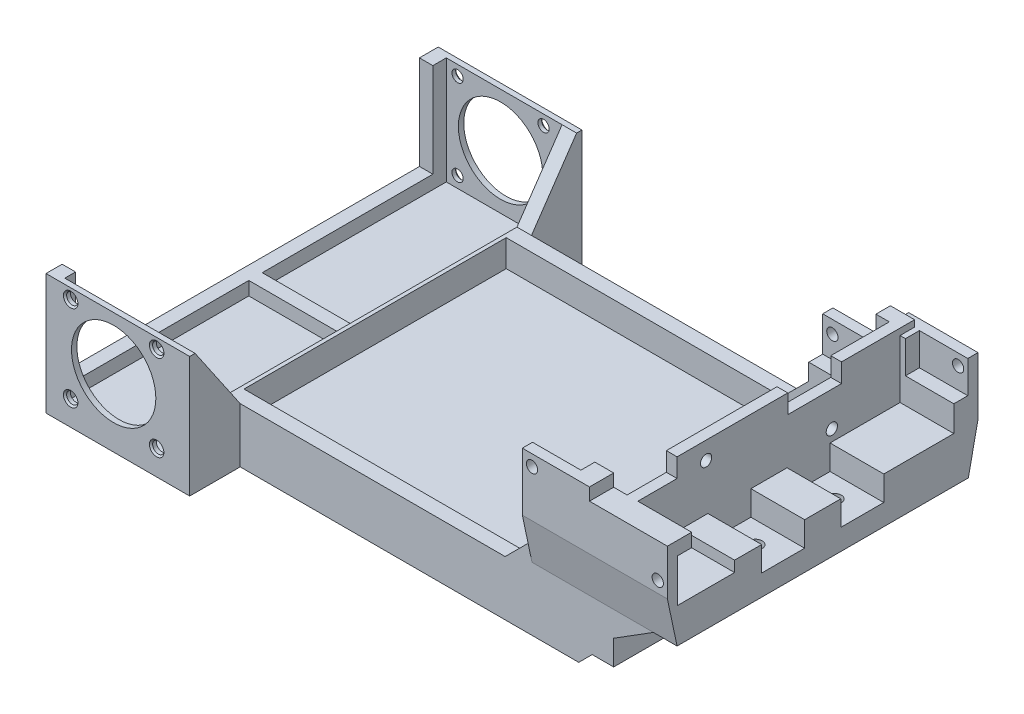
SolidWorks part; units mm, degrees
ref_plane "Front Plane" through (0, 0, 0) normal (0, 0, 1) x (1, 0, 0)
ref_plane "Top Plane" through (0, 0, 0) normal (0, 1, 0) x (1, 0, 0)
ref_plane "Right Plane" through (0, 0, 0) normal (1, 0, 0) x (0, 0, -1)
sketch "Sketch1" plane through (0, 0, 0) normal (0, 1, 0) x (1, 0, 0)
  line L0 (-12.1, 32.5) -> (-12.1, 35.5)
  line L1 (84.3983, -32.4) -> (57.3983, -32.4)
  line L2 (84.3983, -32.4) -> (84.3983, -47)
  line L3 (84.3983, -47) -> (57.3983, -47)
  line L4 (57.3983, -32.4) -> (57.3983, -47)
  line L5 (83.8, 13.5) -> (98.4, 13.5)
  line L6 (83.8, 13.5) -> (83.8, -13.5)
  line L7 (83.8, -13.5) -> (98.4, -13.5)
  line L8 (98.4, 13.5) -> (98.4, -13.5)
  line L9 (57.3983, 32.4) -> (84.3983, 32.4)
  line L10 (57.3983, 32.4) -> (57.3983, 47)
  line L11 (57.3983, 47) -> (84.3983, 47)
  line L12 (84.3983, 32.4) -> (84.3983, 47)
  line L13 (14.3, -24.25) -> (80.8, -24.25)
  line L14 (14.3, -24.25) -> (14.3, 24.25)
  line L15 (14.3, 24.25) -> (80.8, 24.25)
  line L16 (80.8, -24.25) -> (80.8, 24.25)
  line L17 (-12.1, 2.5) -> (10.1, 2.5)
  line L18 (-12.1, 2.5) -> (-12.1, 10.5)
  line L19 (-12.1, 35.5) -> (10.1, 35.5)
  line L20 (10.1, 2.5) -> (10.1, 10.5)
  line L21 (10.1, -35.5) -> (-10.1, -35.5)
  line L22 (10.1, -35.5) -> (10.1, -32.5)
  line L23 (10.1, -2.5) -> (-10.1, -2.5)
  line L24 (-10.1, -35.5) -> (-10.1, -32.5)
  line L25 (-16.1, -32.5) -> (-10.1, -32.5)
  line L26 (-16.1, -32.5) -> (-16.1, -10.5)
  line L27 (-16.1, -10.5) -> (-10.1, -10.5)
  line L28 (11.3, -32.5) -> (11.3, -10.5)
  line L29 (-16.1, 10.5) -> (-12.1, 10.5)
  line L30 (-16.1, 10.5) -> (-16.1, 32.5)
  line L31 (-16.1, 32.5) -> (-12.1, 32.5)
  line L32 (11.3, 10.5) -> (11.3, 32.5)
  line L33 (10.1, 10.5) -> (11.3, 10.5)
  line L34 (10.1, 32.5) -> (10.1, 35.5)
  line L35 (10.1, 32.5) -> (11.3, 32.5)
  line L36 (10.1, -10.5) -> (11.3, -10.5)
  line L37 (10.1, -10.5) -> (10.1, -2.5)
  line L38 (-10.1, -10.5) -> (-10.1, -2.5)
  line L39 (10.1, -32.5) -> (11.3, -32.5)
  arc A0 (86.5992, 6.7139) -> (86.5992, -6.7139) centre (90.3, 0) ccw
  arc A1 (87.5805, -8.0067) -> (93.0195, -8.0067) centre (90.3, -7.366) ccw
  arc A2 (93.0195, 8.0067) -> (87.5805, 8.0067) centre (90.3, 7.366) ccw
  arc A3 (94.0008, -6.7139) -> (94.0008, 6.7139) centre (90.3, 0) ccw
  arc A4 (93.0195, -8.0067) -> (94.0008, -6.7139) centre (94.9662, -8.4654) cw
  arc A5 (86.5992, 6.7139) -> (87.5805, 8.0067) centre (85.6338, 8.4654) ccw
  arc A6 (87.5805, -8.0067) -> (86.5992, -6.7139) centre (85.6338, -8.4654) ccw
  arc A7 (94.0008, 6.7139) -> (93.0195, 8.0067) centre (94.9662, 8.4654) cw
  point P33 (93.085, -7.1425)
  dimension "D1" = 2
  dimension "D2" = 2
  dimension "D3" = 2
  dimension "D36" = 7.6663
  dimension "D37" = 7.366
  dimension "D39" = 2.794
  dimension "D4" = 22.2
  dimension "D5" = 3
  dimension "D6" = 22
  dimension "D7" = 4
  dimension "D8" = 1.2
  dimension "D9" = 3
  dimension "D10" = 66.5
  dimension "D11" = 48.5
  dimension "D12" = 20.2
  dimension "D13" = 6
  dimension "D14" = 1.2
  dimension "D15" = 3
  dimension "D16" = 22
  dimension "D17" = 8
  dimension "D18" = 3
  dimension "D19" = 11.5
  dimension "D20" = 11.5
  dimension "D21" = 27
  dimension "D22" = 14.6
  dimension "D23" = 27
  dimension "D24" = 14.6
  dimension "D26" = 43.0983
  dimension "D27" = 8
  dimension "D28" = 5
  dimension "D29" = 8.15
  dimension "D30" = 3
  dimension "D31" = 10.75
  dimension "D32" = 9.5
  dimension "D33" = 24.25
  dimension "D34" = 27
  dimension "D35" = 14.6
  dimension "D38" = 7.366
  dimension "D40" = 14.3
  dimension "D41" = 2.5
  dimension "D42" = 43.0983
sketch "Sketch5" plane through (0, 0, 0) normal (0, 1, 0) x (1, 0, 0)
  line L0 (83.65, 27.1) -> (11.45, 27.1)
  line L1 (80.8, 24.25) -> (14.3, 24.25) construction
  line L2 (80.8, 24.25) -> (80.8, -24.25) construction
  line L3 (80.8, -24.25) -> (14.3, -24.25) construction
  line L4 (14.3, 24.25) -> (14.3, -24.25) construction
  line L5 (11.45, 27.1) -> (11.45, -27.1)
  line L6 (83.65, -27.1) -> (11.45, -27.1)
  line L7 (83.65, 27.1) -> (83.65, 3.8718)
  line L8 (83.65, -3.8718) -> (83.65, -27.1)
  line L9 (14.15, 24.4) -> (14.15, -24.4)
  line L10 (83.65, 27.1) -> (83.65, -27.1) construction
  line L11 (80.95, -24.4) -> (14.15, -24.4)
  line L12 (80.95, 24.4) -> (80.95, -24.4)
  line L13 (80.95, 24.4) -> (14.15, 24.4)
  arc A0 (83.65, 3.8718) -> (83.65, -3.8718) centre (90.3, 0) ccw
  dimension "D2" = 15.39
  dimension "D1" = 2.85
  dimension "D3" = 0.15
extrude "Boss-Extrude2" add sketch "Sketch5" along normal blind 5
sketch "Sketch6" plane through (0, 0, 0) normal (0, -1, 0) x (1, 0, 0)
  line L0 (83.65, -3.8718) -> (83.65, -27.1)
  line L1 (11.45, 27.1) -> (83.65, 27.1)
  line L2 (11.45, 27.1) -> (11.45, -27.1)
  line L3 (11.45, -27.1) -> (83.65, -27.1)
  line L4 (83.65, 27.1) -> (83.65, 3.8718)
  arc A0 (83.65, 3.8718) -> (83.65, -3.8718) centre (90.3, 0) ccw
  dimension "D1" = 15.39
extrude "Boss-Extrude4" add sketch "Sketch6" along normal blind 2.7
sketch "Sketch7" plane through (0, 5, 0) normal (0, 1, 0) x (1, 0, 0)
  line L1 (83.65, -27.1) -> (75.65, -27.1)
  line L2 (11.45, -27.1) -> (83.65, -27.1) construction
  line L3 (75.65, -27.1) -> (75.65, -24.4)
  line L4 (14.15, -24.4) -> (80.95, -24.4) construction
  line L5 (75.65, -24.4) -> (80.95, -24.4)
  line L6 (80.95, -24.4) -> (80.95, 24.4)
  line L7 (80.95, 24.4) -> (75.65, 24.4)
  line L8 (80.95, 24.4) -> (14.15, 24.4) construction
  line L9 (75.65, 24.4) -> (75.65, 27.1)
  line L10 (83.65, 27.1) -> (11.45, 27.1) construction
  line L11 (75.65, 27.1) -> (83.65, 27.1)
  line L14 (83.65, 27.1) -> (83.65, 3.8718)
  line L15 (83.65, -3.8718) -> (83.65, -27.1)
  arc A0 (83.65, 3.8718) -> (83.65, -3.8718) centre (90.3, 0) ccw
  dimension "D1" = 15.39
  dimension "D2" = 8
  dimension "D3" = 8
extrude "Boss-Extrude5" add sketch "Sketch7" along normal blind 1.575
sketch "Sketch8" plane through (0, 6.575, 0) normal (0, 1, 0) x (1, 0, 0)
  line L0 (75.65, -27.1) -> (83.65, -27.1) construction
  line L1 (80.95, -27.1) -> (98.45, -27.1)
  line L2 (80.95, -27.1) -> (80.95, 27.1)
  line L3 (80.95, 27.1) -> (98.45, 27.1)
  line L4 (98.45, -27.1) -> (98.45, 27.1)
  line L5 (80.95, -27.1) -> (83.65, -27.1) construction
  dimension "D1" = 54.2
  dimension "D2" = 17.5
  dimension "D3" = 2.7
extrude "Boss-Extrude6" add sketch "Sketch8" along normal blind 8.5
sketch "Sketch9" plane through (0, 0, 27.1) normal (0, 0, 1) x (1, 0, 0)
  line L0 (80.95, 15.075) -> (75.65, 6.575)
  line L1 (75.65, 6.575) -> (80.95, 6.575)
  line L2 (80.95, 6.575) -> (80.95, 15.075)
extrude "Boss-Extrude7" add sketch "Sketch9" against normal through all
sketch "Sketch10" plane through (0, 0, 0) normal (0, 1, 0) x (1, 0, 0)
  line L0 (80.95, 27.1) -> (80.95, -27.1) construction
  line L1 (14.15, 24.4) -> (80.95, 24.4)
  line L2 (14.15, 24.4) -> (14.15, -24.4)
  line L3 (14.15, -24.4) -> (80.95, -24.4)
  line L4 (80.95, 24.4) -> (80.95, -24.4)
  line L5 (14.15, -24.4) -> (80.95, -24.4) construction
extrude "Cut-Extrude1" cut sketch "Sketch10" along normal through all
sketch "Sketch11" plane through (0, 0, 27.1) normal (0, 0, 1) x (1, 0, 0)
  line L0 (91.05, 6.575) -> (83.65, 1.9375)
  line L1 (83.65, 6.575) -> (98.45, 6.575) construction
  line L2 (83.65, 6.575) -> (83.65, -2.7) construction
  line L3 (83.65, 1.9375) -> (83.65, 6.575)
  line L4 (83.65, 6.575) -> (91.05, 6.575)
extrude "Boss-Extrude8" add sketch "Sketch11" against normal blind 5
sketch "Sketch12" plane through (0, 0, -27.1) normal (0, 0, -1) x (-1, 0, 0)
  line L0 (-91.05, 6.575) -> (-83.65, 1.9375)
  line L1 (-98.45, 6.575) -> (-83.65, 6.575) construction
  line L2 (-83.65, 6.575) -> (-83.65, -2.7) construction
  line L3 (-83.65, 1.9375) -> (-83.65, 6.575)
  line L4 (-83.65, 6.575) -> (-91.05, 6.575)
extrude "Boss-Extrude9" add sketch "Sketch12" against normal blind 5
sketch "Sketch13" plane through (0, 15.075, 0) normal (0, 1, 0) x (1, 0, 0)
  line L1 (80.95, 27.1) -> (85.45, 27.1)
  line L2 (80.95, 27.1) -> (80.95, -27.1)
  line L3 (80.95, -27.1) -> (85.45, -27.1)
  line L4 (85.45, 27.1) -> (85.45, -27.1)
  dimension "D1" = 4.5
extrude "Boss-Extrude10" add sketch "Sketch13" along normal blind 12
sketch "Sketch15" plane through (0, 15.075, 0) normal (0, 1, 0) x (1, 0, 0)
  circle A0 centre (90.3, 7.366) radius 1.25
  circle A1 centre (90.3, -7.366) radius 1.25
  dimension "D1" = 2.5
  dimension "D2" = 2.5
extrude "Cut-Extrude3" cut sketch "Sketch15" against normal through all
sketch "Sketch16" plane through (0, 15.075, 0) normal (0, 1, 0) x (1, 0, 0)
  line L0 (90.3, -7.366) -> (90.3, 7.366) construction
  line L1 (90.3, -7.366) -> (85.45, -7.366) construction
  line L2 (85.45, -27.1) -> (85.45, 27.1) construction
  line L3 (85.45, -7.366) -> (85.45, -11.366) construction
  line L4 (90.3, 7.366) -> (85.45, 7.366) construction
  line L5 (85.45, -27.1) -> (85.45, 27.1) construction
  line L6 (85.45, 7.366) -> (85.45, 11.366) construction
  line L7 (98.45, -27.1) -> (98.45, 27.1) construction
  line L8 (85.45, 11.366) -> (98.45, 11.366)
  line L9 (85.45, 11.366) -> (85.45, 3.366)
  line L10 (85.45, -11.366) -> (98.45, -11.366)
  line L11 (98.45, 11.366) -> (98.45, 3.366)
  line L12 (85.45, -7.366) -> (85.45, -3.366) construction
  line L13 (85.45, -3.366) -> (98.45, -3.366)
  line L14 (85.45, 7.366) -> (85.45, 3.366) construction
  line L15 (85.45, 3.366) -> (98.45, 3.366)
  line L16 (85.45, -3.366) -> (85.45, -11.366)
  line L17 (98.45, -3.366) -> (98.45, -11.366)
  dimension "D1" = 4
  dimension "D2" = 4
  dimension "D3" = 4
  dimension "D4" = 4
extrude "Cut-Extrude4" cut sketch "Sketch16" against normal offset from surface (4.6 mm away) 3.9 up to face at (90.3, 6.575, -8.616)
sketch "Sketch17" plane through (0, 15.075, 0) normal (0, 1, 0) x (1, 0, 0)
  line L0 (85.45, -27.1) -> (98.45, -27.1) construction
  line L1 (98.45, 27.1) -> (95.45, 27.1)
  line L2 (98.45, 27.1) -> (98.45, -27.1)
  line L3 (98.45, -27.1) -> (95.45, -27.1)
  line L4 (95.45, 27.1) -> (95.45, -27.1)
  dimension "D1" = 3
extrude "Cut-Extrude5" cut sketch "Sketch17" against normal through all
sketch "Sketch18" plane through (80.95, 0, 0) normal (-1, 0, 0) x (0, 0, 1)
  line L0 (0, 27.075) -> (-13.5, 27.075) construction
  line L1 (-27.1, 27.075) -> (27.1, 27.075) construction
  line L3 (-13.5, 27.075) -> (-3.5, 27.075)
  line L4 (-13.5, 27.075) -> (-13.5, 23.575)
  line L5 (-13.5, 23.575) -> (-3.5, 23.575)
  line L6 (-3.5, 27.075) -> (-3.5, 23.575)
  dimension "D1" = 13.5
  dimension "D2" = 8.5
  dimension "D3" = 10
extrude "Cut-Extrude6" cut sketch "Sketch18" against normal through all
sketch "Sketch19" plane through (85.45, 0, 0) normal (1, 0, 0) x (0, 0, -1)
  line L0 (-27.1, 27.075) -> (27.1, 27.075) construction
  line L1 (0, 15.075) -> (0, 25.875) construction
  line L3 (-11.7, 20.475) -> (11.7, 20.475) construction
  line L4 (11.7, 20.475) -> (11.7, 17.175) construction
  line L5 (-11.7, 20.475) -> (-11.7, 23.775) construction
  line L7 (0, 27.075) -> (0, 25.875) construction
  line L8 (3.366, 15.075) -> (-3.366, 15.075) construction
  circle A0 centre (-11.7, 23.775) radius 1.05
  circle A1 centre (11.7, 17.175) radius 1.05
  point P11 (0, 20.475)
  point P15 (0, 20.475)
  dimension "D3" = 2.1
  dimension "D4" = 2.1
  dimension "D1" = 23.4
  dimension "D2" = 2.1
  dimension "D5" = 10.8
extrude "Cut-Extrude7" cut sketch "Sketch19" against normal through all
sketch "Sketch20" plane through (0, 27.075, 0) normal (0, 1, 0) x (1, 0, 0)
  line L2 (80.95, -24.4) -> (80.95, 24.4)
  line L4 (83.45, -24.4) -> (83.45, 24.4)
  line L5 (80.95, 27.1) -> (80.95, 24.4) construction
  line L6 (80.95, 24.4) -> (83.45, 24.4)
  line L7 (80.95, -27.1) -> (80.95, -24.4) construction
  line L8 (80.95, -24.4) -> (83.45, -24.4)
  dimension "D1" = 2
extrude "Cut-Extrude8" cut sketch "Sketch20" against normal blind 20
sketch "Sketch21" plane through (0, 0, 27.1) normal (0, 0, 1) x (1, 0, 0)
  line L0 (95.45, 15.075) -> (95.45, 17.175) construction
  line L1 (85.45, 15.075) -> (95.45, 15.075)
  line L2 (85.45, 15.075) -> (85.45, 20.075)
  line L3 (85.45, 20.075) -> (95.45, 20.075)
  line L4 (95.45, 15.075) -> (95.45, 20.075)
  line L5 (95.45, 17.175) -> (93.65, 17.175) construction
  line L6 (95.45, 6.575) -> (95.45, 15.075) construction
  circle A0 centre (93.65, 17.175) radius 1.05
  dimension "D4" = 2.1
  dimension "D1" = 5
  dimension "D2" = 2.1
  dimension "D3" = 1.8
extrude "Boss-Extrude11" add sketch "Sketch21" against normal blind 2.7 and the other way blind 1.8
sketch "Sketch23" plane through (0, 0, 27.1) normal (0, 0, 1) x (1, 0, 0)
  line L0 (68.45, 25.875) -> (68.45, 23.775) construction
  line L1 (95.45, 15.075) -> (68.45, 15.075)
  line L2 (95.45, 15.075) -> (95.45, 25.875)
  line L3 (95.45, 25.875) -> (68.45, 25.875)
  line L4 (68.45, 15.075) -> (68.45, 25.875)
  line L5 (68.45, 23.775) -> (70.25, 23.775) construction
  circle A0 centre (70.25, 23.775) radius 1.05
  circle A1 centre (93.65, 17.175) radius 1.05
  dimension "D5" = 2.1
  dimension "D6" = 2.1
  dimension "D1" = 10.8
  dimension "D2" = 27
  dimension "D3" = 2.1
  dimension "D4" = 1.8
extrude "Boss-Extrude13" add sketch "Sketch23" along normal blind 1.8 and the other way blind 2.7
sketch "Sketch22" plane through (83.45, 0, 0) normal (-1, 0, 0) x (0, 0, 1)
  line L1 (34.4916, 27.075) -> (17.1, 27.075)
  line L3 (27.9666, 23.575) -> (17.1, 23.575)
  line L4 (17.1, 27.075) -> (17.1, 23.575)
  line L5 (34.4916, 27.075) -> (34.4916, 23.575)
  line L6 (34.4916, 23.575) -> (27.9666, 23.575)
  line L7 (27.1, 27.075) -> (-3.5, 27.075) construction
  dimension "D1" = 10
  dimension "D3" = 3.5
extrude "Cut-Extrude9" cut sketch "Sketch22" against normal through all and the other way up to surface (2.5 mm away) other way up to face at (80.95, 26.475, 25.75)
sketch "Sketch24" plane through (0, 0, 27.1) normal (0, 0, 1) x (1, 0, 0)
  line L1 (68.45, 15.075) -> (85.45, 15.075)
  line L2 (68.45, 15.075) -> (68.45, 5)
  line L3 (68.45, 5) -> (85.45, 5)
  line L4 (85.45, 15.075) -> (85.45, 5)
extrude "Boss-Extrude14" add sketch "Sketch24" against normal up to surface (2.7 mm away) up to face at (68.3192, 12.2904, 24.4)
sketch "Sketch25" plane through (0, 0, -27.1) normal (0, 0, -1) x (-1, 0, 0)
  line L0 (-95.45, 25.875) -> (-95.45, 23.775) construction
  line L1 (-95.45, 15.075) -> (-68.45, 15.075)
  line L2 (-95.45, 15.075) -> (-95.45, 25.875)
  line L3 (-95.45, 25.875) -> (-82.55, 25.875)
  line L5 (-95.45, 23.775) -> (-93.65, 23.775) construction
  line L6 (-68.45, 15.075) -> (-68.45, 17.175) construction
  line L7 (-68.45, 17.175) -> (-70.25, 17.175) construction
  line L9 (-68.45, 19.575) -> (-77.45, 19.575)
  line L10 (-77.45, 19.575) -> (-82.55, 25.875)
  line L11 (-68.45, 19.575) -> (-68.45, 15.075)
  circle A0 centre (-93.65, 23.775) radius 1.05
  circle A1 centre (-70.25, 17.175) radius 1.05
  dimension "D3" = 2.1
  dimension "D1" = 2.1
  dimension "D2" = 1.8
  dimension "D4" = 2.1
  dimension "D5" = 1.8
  dimension "D6" = 4.5
  dimension "D7" = 9
  dimension "D8" = 27
  dimension "D9" = 12.9
  dimension "D10" = 6.3
extrude "Boss-Extrude15" add sketch "Sketch25" along normal blind 1.8 and the other way blind 2.7
sketch "Sketch26" plane through (0, 0, -24.4) normal (0, 0, 1) x (1, 0, 0)
  line L0 (80.95, 15.075) -> (68.45, 15.075) construction
  line L1 (68.45, 19.575) -> (80.95, 19.575)
  line L2 (68.45, 19.575) -> (68.45, 15.075)
  line L3 (68.45, 15.075) -> (80.95, 15.075)
  line L4 (80.95, 19.575) -> (80.95, 15.075)
extrude "Cut-Extrude10" cut sketch "Sketch26" against normal blind 2.6
sketch "Sketch27" plane through (0, 0, 24.4) normal (0, 0, -1) x (-1, 0, 0)
  line L1 (-68.45, 25.875) -> (-77.45, 25.875)
  line L2 (-68.45, 25.875) -> (-68.45, 19.875)
  line L3 (-68.45, 19.875) -> (-77.45, 19.875)
  line L4 (-77.45, 25.875) -> (-77.45, 19.875)
  dimension "D1" = 6
  dimension "D2" = 9
extrude "Cut-Extrude11" cut sketch "Sketch27" against normal blind 2.6
sketch "Sketch28" plane through (0, 0, -24.4) normal (0, 0, 1) x (1, 0, 0)
  line L1 (95.45, 25.875) -> (86.45, 25.875)
  line L2 (95.45, 25.875) -> (95.45, 19.875)
  line L3 (95.45, 19.875) -> (86.45, 19.875)
  line L4 (86.45, 25.875) -> (86.45, 19.875)
  dimension "D1" = 6
  dimension "D2" = 9
extrude "Cut-Extrude12" cut sketch "Sketch28" against normal blind 2.6
sketch "Sketch29" plane through (0, 0, 24.4) normal (0, 0, -1) x (-1, 0, 0)
  line L0 (-95.45, 15.075) -> (-95.45, 13.075)
  line L2 (-95.45, 15.075) -> (-95.45, 21.075)
  line L3 (-95.45, 21.075) -> (-86.45, 21.075)
  line L5 (-95.45, 13.075) -> (-86.45, 13.075)
  line L6 (-86.45, 13.075) -> (-86.45, 21.075)
  dimension "D1" = 6
  dimension "D2" = 9
  dimension "D3" = 2
extrude "Cut-Extrude13" cut sketch "Sketch29" against normal blind 2.6 and the other way blind 8
sketch "Sketch30" plane through (0, 0, -27.1) normal (0, 0, -1) x (-1, 0, 0)
  line L1 (-68.45, 15.075) -> (-86.6707, 15.075)
  line L2 (-68.45, 15.075) -> (-68.45, 5)
  line L3 (-68.45, 5) -> (-86.6707, 5)
  line L4 (-86.6707, 15.075) -> (-86.6707, 5)
extrude "Boss-Extrude16" add sketch "Sketch30" against normal blind 2.7
sketch "Sketch31" plane through (0, -2.7, 0) normal (0, -1, 0) x (1, 0, 0)
  line L0 (83.65, 27.1) -> (77.15, 27.1) construction
  line L1 (83.65, 27.1) -> (11.45, 27.1) construction
  line L3 (77.15, 27.1) -> (-12.5923, 27.1)
  line L4 (77.15, 27.1) -> (77.15, -27.7093)
  line L5 (77.15, -27.7093) -> (-12.5923, -27.7093)
  line L6 (-12.5923, 27.1) -> (-12.5923, -27.7093)
  dimension "D1" = 6.5
  dimension "D2" = 24.05
extrude "Boss-Extrude17" add sketch "Sketch31" along normal blind 2.5
sketch "Sketch33" plane through (0, -5.2, 0) normal (0, -1, 0) x (1, 0, 0)
  line L0 (-12.6, 0) -> (0, 0) construction
  line L1 (-12.5923, 27.1) -> (-12.5923, -27.7093) construction
  line L2 (-12.6, -1.25) -> (11.45, -1.25)
  line L3 (-12.6, 1.25) -> (11.45, 1.25)
  line L4 (0, 0) -> (11.45, 0) construction
  line L5 (11.45, 27.1) -> (11.45, -27.1) construction
  line L6 (-12.6, -1.25) -> (0, -1.25) construction
  line L7 (-12.6, 1.25) -> (0, 1.25) construction
  line L8 (-12.6, 1.25) -> (-12.6, -1.25)
  line L9 (11.45, 1.25) -> (11.45, -1.25)
  dimension "D1" = 1.25
  dimension "D2" = 1.25
extrude "Boss-Extrude18" add sketch "Sketch33" against normal blind 5
sketch "Sketch36" plane through (0, -5.2, 0) normal (0, -1, 0) x (1, 0, 0)
  line L1 (-12.5923, 27.1) -> (11.45, 27.1)
  line L2 (-12.5923, 27.1) -> (-12.5923, 36.5)
  line L3 (-12.5923, 36.5) -> (11.45, 36.5)
  line L4 (11.45, 27.1) -> (11.45, 36.5)
  dimension "D1" = 9.4
extrude "Boss-Extrude20" add sketch "Sketch36" against normal up to surface (2.5 mm away) up to face at (-0.5711, -2.7, 14.175)
sketch "Sketch37" plane through (0, -2.7, 0) normal (0, 1, 0) x (1, 0, 0)
  line L0 (11.45, -27.1) -> (11.45, -36.5) construction
  line L1 (-12.5923, -36.5) -> (11.45, -36.5)
  line L2 (-12.5923, -36.5) -> (-12.5923, -35.5)
  line L3 (-12.5923, -35.5) -> (11.45, -35.5)
  line L4 (11.45, -36.5) -> (11.45, -35.5)
  dimension "D1" = 1
extrude "Boss-Extrude21" add sketch "Sketch37" along normal blind 20
sketch "Sketch38" plane through (0, 0, 36.5) normal (0, 0, 1) x (1, 0, 0)
  line L0 (0, 17.3) -> (8, 17.3) construction
  line L1 (-12.5923, 17.3) -> (11.45, 17.3) construction
  line L2 (8, 17.3) -> (8, 15.4) construction
  line L3 (8, 15.4) -> (-8, 15.4) construction
  line L4 (8, 15.4) -> (8, -0.6) construction
  line L5 (-8, 15.4) -> (-8, -0.6) construction
  line L6 (-8, -0.6) -> (-8, 7.4) construction
  line L7 (-8, 7.4) -> (0, 7.4) construction
  circle A0 centre (8, 15.4) radius 1.05
  circle A1 centre (8, -0.6) radius 1.05
  circle A2 centre (-8, 15.4) radius 1.05
  circle A3 centre (-8, -0.6) radius 1.05
  circle A4 centre (0, 7.4) radius 7.85
  dimension "D3" = 2.1
  dimension "D8" = 15.7
  dimension "D1" = 8
  dimension "D2" = 1.9
  dimension "D4" = 16
  dimension "D5" = 16
  dimension "D6" = 16
  dimension "D7" = 8
extrude "Cut-Extrude14" cut sketch "Sketch38" against normal up to next
sketch "Sketch39" plane through (0, -2.7, 0) normal (0, 1, 0) x (1, 0, 0)
  line L0 (11.45, -27.1) -> (68.45, -27.1) construction
  line L1 (11.45, -36.5) -> (14.15, -36.5)
  line L2 (11.45, -36.5) -> (11.45, -27.1)
  line L3 (11.45, -27.1) -> (14.15, -27.1)
  line L4 (14.15, -36.5) -> (14.15, -27.1)
  dimension "D1" = 2.7
extrude "Boss-Extrude22" add sketch "Sketch39" along normal up to surface (7.7 mm away) and the other way up to surface (2.5 mm away) up to face at (40.625, 5, 0) other way up to face at (10.1631, -5.2, 7.1781)
sketch "Sketch40" plane through (0, 5, 0) normal (0, 1, 0) x (1, 0, 0)
  line L1 (14.15, -36.5) -> (11.45, -36.5)
  line L2 (14.15, -36.5) -> (14.15, -35.5)
  line L3 (14.15, -35.5) -> (11.45, -35.5)
  line L4 (11.45, -36.5) -> (11.45, -35.5)
extrude "Boss-Extrude23" add sketch "Sketch40" along normal up to surface (12.3 mm away) up to face at (-0.5711, 17.3, 36)
sketch "Sketch41" plane through (14.15, 0, 0) normal (1, 0, 0) x (0, 0, -1)
  line L0 (-27.1, 5) -> (-35.5, 17.3)
  line L1 (-35.5, 17.3) -> (-35.5, 5)
  line L2 (-35.5, 5) -> (-27.1, 5)
extrude "Boss-Extrude24" add sketch "Sketch41" against normal up to surface (2.7 mm away) up to face at (11.45, -0.15, 2.1)
sketch "Sketch42" plane through (0, -2.7, 0) normal (0, 1, 0) x (1, 0, 0)
  line L1 (-12.5923, -35.5) -> (-10.0923, -35.5)
  line L2 (-12.5923, -35.5) -> (-12.5923, -33.5)
  line L3 (-12.5923, -33.5) -> (-10.0923, -33.5)
  line L4 (-10.0923, -35.5) -> (-10.0923, -33.5)
  dimension "D1" = 2.5
  dimension "D2" = 2
extrude "Boss-Extrude25" add sketch "Sketch42" along normal up to surface (20 mm away) up to face at (2.9131, 17.3, 35.9)
sketch "Sketch43" plane through (0, -2.7, 0) normal (0, 1, 0) x (1, 0, 0)
  line L1 (-12.6, 27.1) -> (11.45, 27.1)
  line L2 (-12.6, 27.1) -> (-12.6, 36.5)
  line L3 (-12.6, 36.5) -> (11.45, 36.5)
  line L4 (11.45, 27.1) -> (11.45, 36.5)
  dimension "D1" = 9.4
extrude "Boss-Extrude26" add sketch "Sketch43" against normal up to surface (2.5 mm away) up to face at (10.7031, -5.2, 7.1781)
sketch "Sketch44" plane through (0, -2.7, 0) normal (0, 1, 0) x (1, 0, 0)
  line L0 (11.45, 27.7093) -> (11.45, 36.5) construction
  line L1 (-12.6, 36.5) -> (11.45, 36.5)
  line L2 (-12.6, 36.5) -> (-12.6, 35.5)
  line L3 (-12.6, 35.5) -> (11.45, 35.5)
  line L4 (11.45, 36.5) -> (11.45, 35.5)
  dimension "D1" = 1
extrude "Boss-Extrude27" add sketch "Sketch44" along normal up to surface (20 mm away) up to face at (-0.8027, 17.3, 35.2143)
sketch "Sketch45" plane through (0, -2.7, 0) normal (0, 1, 0) x (1, 0, 0)
  line L0 (68.45, 27.1) -> (11.45, 27.1) construction
  line L1 (11.45, 36.5) -> (14.15, 36.5)
  line L2 (11.45, 36.5) -> (11.45, 27.1)
  line L3 (11.45, 27.1) -> (14.15, 27.1)
  line L4 (14.15, 36.5) -> (14.15, 27.1)
  dimension "D1" = 2.7
extrude "Boss-Extrude30" add sketch "Sketch45" along normal up to surface (7.7 mm away) and the other way up to surface (2.5 mm away) up to face at (37.6833, 5, 3.0111) other way up to face at (7.4808, -5.2, -3.9585)
sketch "Sketch46" plane through (14.15, 0, 0) normal (1, 0, 0) x (0, 0, -1)
  line L0 (27.1, 5) -> (35.5, 17.3)
  line L1 (35.5, 17.3) -> (36.5, 17.3)
  line L2 (36.5, 17.3) -> (36.5, 5)
  line L3 (36.5, 5) -> (27.1, 5)
extrude "Boss-Extrude31" add sketch "Sketch46" against normal up to surface (2.7 mm away) up to face at (11.45, 11.15, -36)
sketch "Sketch47" plane through (0, -2.7, 0) normal (0, 1, 0) x (1, 0, 0)
  line L1 (-12.6, 35.5) -> (-10.1, 35.5)
  line L2 (-12.6, 35.5) -> (-12.6, 33)
  line L3 (-12.6, 33) -> (-10.1, 33)
  line L4 (-10.1, 35.5) -> (-10.1, 33)
  dimension "D1" = 2.5
  dimension "D2" = 2.5
extrude "Boss-Extrude32" add sketch "Sketch47" along normal up to surface (20 mm away) up to face at (2.91, 17.3, -35.9)
sketch "Sketch48" plane through (0, 0, -36.5) normal (0, 0, -1) x (-1, 0, 0)
  line L0 (0, 0) -> (0, 17.3) construction
  line L1 (12.6, 17.3) -> (-14.15, 17.3) construction
  line L2 (0, 17.3) -> (8, 17.3) construction
  line L3 (8, 17.3) -> (8, 15.4) construction
  line L4 (8, 15.4) -> (-8, 15.4) construction
  line L5 (-8, 15.4) -> (-8, -0.6) construction
  line L6 (8, 15.4) -> (8, -0.6) construction
  line L7 (8, 7.4) -> (0, 7.4) construction
  circle A0 centre (8, 15.4) radius 1.05
  circle A1 centre (-8, 15.4) radius 1.05
  circle A2 centre (-8, -0.6) radius 1.05
  circle A3 centre (8, -0.6) radius 1.05
  circle A4 centre (0, 7.4) radius 7.85
  dimension "D3" = 2.1
  dimension "D7" = 15.7
  dimension "D1" = 8
  dimension "D2" = 1.9
  dimension "D4" = 16
  dimension "D5" = 16
  dimension "D6" = 16
extrude "Cut-Extrude15" cut sketch "Sketch48" against normal up to surface (1 mm away) up to face at (0.675, 7.3, -35.5)
sketch "Sketch49" plane through (0, -2.7, 0) normal (0, 1, 0) x (1, 0, 0)
  line L1 (-10.1, 33) -> (-12.5923, 33)
  line L2 (-10.1, 33) -> (-10.1, -33.5)
  line L3 (-10.1, -33.5) -> (-12.5923, -33.5)
  line L4 (-12.5923, 33) -> (-12.5923, -33.5)
extrude "Boss-Extrude33" add sketch "Sketch49" along normal blind 2.5
chamfer "Chamfer1" distance 0.3 angle 45 8 edges at (-9.05, 15.4, -36.5) (6.95, -0.6, -36.5) (-9.05, -0.6, -36.5) (6.95, 15.4, -36.5) (-6.95, -0.6, 36.5) (9.05, -0.6, 36.5) (9.05, 15.4, 36.5) (-6.95, 15.4, 36.5)
chamfer "Chamfer2" distance 2.5 angle 45 1 edges at (77.15, -2.7, 0)
chamfer "Chamfer3" distance 5 angle 45 2 edges at (68.45, 5, -25.75) (68.45, 5, 25.75)
sketch "Sketch50" plane through (0, 15.075, 0) normal (0, 1, 0) x (1, 0, 0)
  line L1 (68.45, 24.4) -> (80.95, 24.4)
  line L2 (68.45, 24.4) -> (68.45, 27)
  line L3 (68.45, 27) -> (80.95, 27)
  line L4 (80.95, 24.4) -> (80.95, 27)
extrude "Cut-Extrude16" cut sketch "Sketch50" against normal blind 2
sketch "Sketch51" plane through (95.45, 0, 0) normal (1, 0, 0) x (0, 0, -1)
  line L0 (-28.9, 15.075) -> (-27.1, 6.575)
  line L1 (-27.1, 6.575) -> (-27.1, 15.075)
  line L2 (-27.1, 15.075) -> (-28.9, 15.075)
extrude "Boss-Extrude34" add sketch "Sketch51" against normal up to surface (27 mm away) up to face at (68.45, 17.7063, 26.85)
sketch "Sketch52" plane through (95.45, 0, 0) normal (1, 0, 0) x (0, 0, -1)
  line L0 (28.9, 15.075) -> (27.1, 6.575)
  line L1 (27.1, 6.575) -> (27.1, 15.075)
  line L2 (27.1, 15.075) -> (28.9, 15.075)
extrude "Boss-Extrude35" add sketch "Sketch52" against normal up to surface (27 mm away) up to face at (68.45, 14.4312, -26.85)
sketch "Sketch53" plane through (0, 5, 0) normal (0, 1, 0) x (1, 0, 0)
  line L0 (14.15, -24.4) -> (80.95, -24.4) construction
  line L1 (14.15, 24.4) -> (12.15, 24.4)
  line L2 (14.15, 24.4) -> (14.15, -24.4)
  line L3 (14.15, -24.4) -> (12.15, -24.4)
  line L4 (12.15, 24.4) -> (12.15, -24.4)
  dimension "D1" = 2
extrude "Cut-Extrude17" cut sketch "Sketch53" against normal up to surface (5 mm away) up to face at (47.55, 0, 0)
